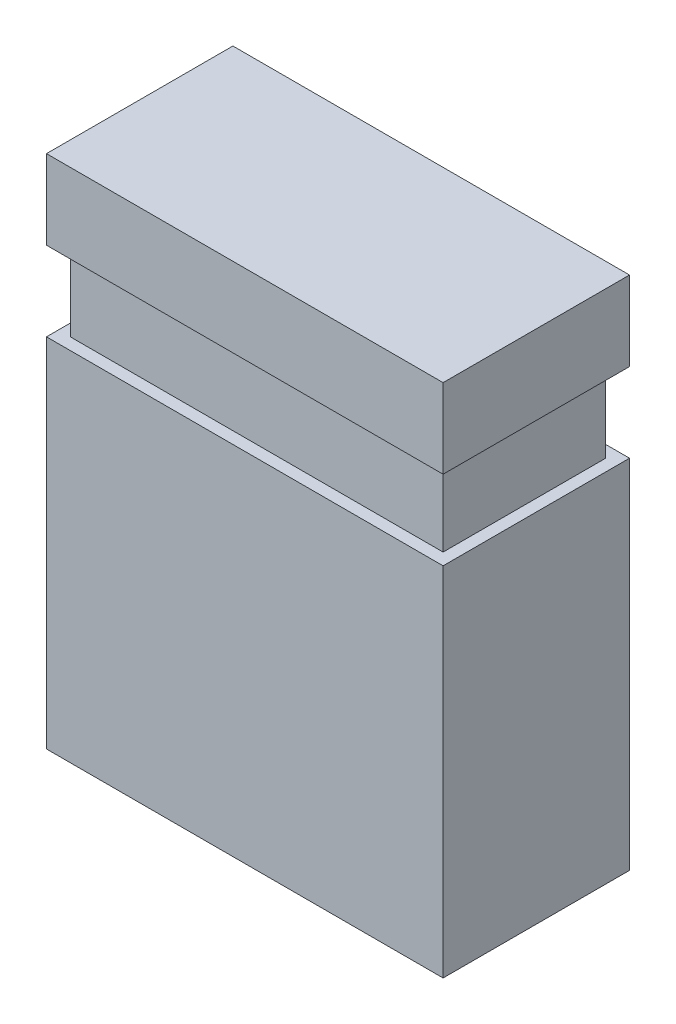
SolidWorks part; units mm, degrees
ref_plane "Front" through (0, 0, 0) normal (0, 0, 1) x (1, 0, 0)
ref_plane "Top" through (0, 0, 0) normal (0, 1, 0) x (1, 0, 0)
ref_plane "Right" through (0, 0, 0) normal (1, 0, 0) x (0, 0, -1)
sketch "Sketch1" plane through (0, 0, 0) normal (0, 0, 1) x (1, 0, 0)
  line L1 (-2.5, 3.25) -> (2.5, 3.25)
  line L2 (-2.5, 3.25) -> (-2.5, -3.25)
  line L3 (-2.5, -3.25) -> (2.5, -3.25)
  line L4 (2.5, 3.25) -> (2.5, -3.25)
  point P4 (0, 3.25)
  point P6 (-2.5, 0)
  dimension "D1" = 6.5
  dimension "D2" = 5
extrude "Extrude1" add sketch "Sketch1" along normal blind 1.175 and the other way blind 1.175
sketch "Sketch2" plane through (0, 3.25, 0) normal (0, 1, 0) x (1, 0, 0)
  line L0 (2.5, 1.175) -> (-2.5, 1.175) construction
  line L1 (-2.35, 1.025) -> (2.35, 1.025)
  line L2 (-2.35, 1.025) -> (-2.35, -1.025)
  line L3 (-2.35, -1.025) -> (2.35, -1.025)
  line L4 (2.35, 1.025) -> (2.35, -1.025)
  line L5 (2.5, -1.175) -> (-2.5, -1.175) construction
  line L6 (-2.5, 1.175) -> (-2.5, -1.175) construction
  line L7 (2.5, 1.175) -> (2.5, -1.175) construction
  dimension "D1" = 0.15
  dimension "D2" = 0.15
  dimension "D3" = 0.15
  dimension "D4" = 0.15
extrude "Cut-Extrude1" cut sketch "Sketch2" against normal blind 1 from offset 1 flip side to cut offset against normal yes
sketch "Sketch3" plane through (0, -3.25, 0) normal (0, -1, 0) x (1, 0, 0)
  line L0 (-2.5, 1.175) -> (2.5, 1.175) construction
  line L1 (-2, 0.675) -> (2, 0.675)
  line L2 (-2, 0.675) -> (-2, -0.675)
  line L3 (-2, -0.675) -> (2, -0.675)
  line L4 (2, 0.675) -> (2, -0.675)
  line L5 (-2.5, -1.175) -> (2.5, -1.175) construction
  line L6 (-2.5, -1.175) -> (-2.5, 1.175) construction
  line L7 (2.5, -1.175) -> (2.5, 1.175) construction
  dimension "D1" = 0.5
  dimension "D2" = 0.5
  dimension "D3" = 0.5
  dimension "D4" = 0.5
extrude "Cut-Extrude2" cut sketch "Sketch3" against normal blind 4
sketch "Component_Outline" plane through (0, -3.25, 0) normal (0, -1, 0) x (1, 0, 0)
  line L8 (2.5, -1.175) -> (2.5, 1.175)
  line L9 (2.5, 1.175) -> (-2.5, 1.175)
  line L10 (-2.5, 1.175) -> (-2.5, -1.175)
  line L11 (-2.5, -1.175) -> (2.5, -1.175)
  line L12 (2.5, -1.175) -> (2.5, 1.175)
  line L13 (2.5, 1.175) -> (-2.5, 1.175)
  line L14 (-2.5, 1.175) -> (-2.5, -1.175)
  line L15 (-2.5, -1.175) -> (2.5, -1.175)
  dimension "D1" = 0
